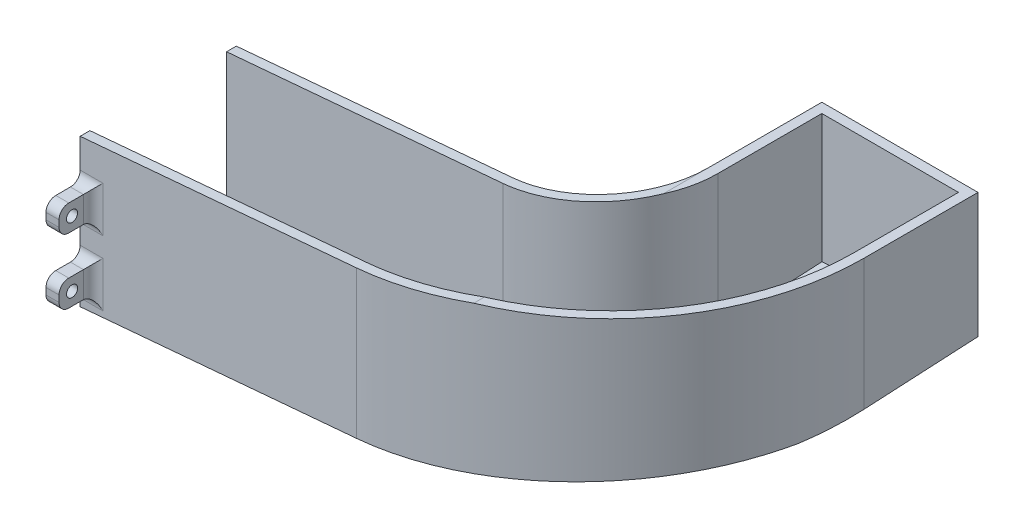
SolidWorks part; units mm, degrees
ref_plane "Front Plane" through (0, 0, 0) normal (0, 0, 1) x (1, 0, 0)
ref_plane "Top Plane" through (0, 0, 0) normal (0, 1, 0) x (1, 0, 0)
ref_plane "Right Plane" through (0, 0, 0) normal (1, 0, 0) x (0, 0, -1)
sketch "Sketch2" plane through (0, 0, 0) normal (0, 1, 0) x (1, 0, 0)
  line L1 (0, 0) -> (85, 0)
  line L2 (0, 0) -> (0, 48)
  line L3 (0, 48) -> (85, 48)
  line L8 (115, 78) -> (115, 113)
  line L9 (115, 113) -> (163, 113)
  line L10 (163, 78) -> (163, 113)
  arc A1 (85, 48) -> (115, 78) centre (85, 78) ccw
  arc A2 (85, 0) -> (163, 78) centre (85, 78) ccw
  point P9 (0, 0)
  point P11 (0, 0)
  dimension "D1" = 48
  dimension "D5" = 35
  dimension "D2" = 85
  dimension "D3" = 48
  dimension "D4" = 115
extrude "Boss-Extrude1" add sketch "Sketch2" along normal blind 60
sketch "Sketch3" plane through (0, 0, 0) normal (0, 0, 1) x (1, 0, 0)
  line L0 (0, 0) -> (200, 17.4977)
  line L2 (0, 60) -> (0, 0) construction
  line L3 (200, 0) -> (200, 17.4977)
  line L5 (0, 0) -> (200, 0)
  line L7 (0, 45.39) -> (0, 60)
  line L8 (0, 60) -> (200, 60)
  line L9 (0, 60) -> (85, 60) construction
  line L11 (163, 60) -> (85, 60) construction
  line L12 (0, 45.39) -> (115, 55.4512)
  line L13 (115, 55.4512) -> (200, 55.4512)
  line L14 (200, 55.4512) -> (200, 60)
  point P4 (140.9944, 57.1439)
  point P14 (154.6463, 60)
  point P17 (180.8999, 60)
  point P18 (132.5245, 57.8644)
  point P21 (113.8292, 56.2288)
  point P23 (0, 0)
  dimension "D1" = 45.39
  dimension "D2" = 200
  dimension "D3" = 5
extrude "Cut-Extrude1" cut sketch "Sketch3" against normal through all
sketch "Sketch18" plane through (163, 0, 0) normal (-1, 0, 0) x (0, 0, 1)
  line L0 (-123, 8.2607) -> (-53, 8.2607)
  line L4 (-123, 8.2607) -> (-123, 17.5692)
  line L5 (-48, 45.39) -> (-48, 0) construction
  line L6 (-78, 14.2607) -> (-113, 14.2607) construction
  line L7 (-53, 8.2607) -> (-53, 13.9006)
  line L8 (-53, 13.9006) -> (-123, 17.5692)
  ellipse E3 centre (-78, 7.4365) end of major axis (0, 7.4365) minor radius 6.8241 (0, 7.4365) -> (-78, 14.2607) ccw construction
  dimension "D1" = 3
  dimension "D2" = 70
  dimension "D3" = 6
  dimension "D4" = 5
extrude "Cut-Extrude9" cut sketch "Sketch18" along direction (-0.9962, -0.0872, 0) on the side against the normal blind 55 and the other way blind 55
shell "Shell4" thickness 3 removed face at (67.7517, 51.3175, -28.7169) removed face at (136.38, 55.4512, -76.1467)
sketch "Sketch15" plane through (3, 0, 0) normal (1, 0, 0) x (0, 0, -1)
  line L4 (45, 45.6525) -> (3, 45.6525)
  line L5 (45, 45.6525) -> (3, 45.6525)
  line L8 (3, 45.6525) -> (3, 3.2739)
  line L9 (3, 3.2739) -> (45, 3.2739)
  line L10 (45, 3.2739) -> (45, 45.6525)
  line L12 (3, 45.6525) -> (3, 3.2739)
  line L13 (3, 3.2739) -> (45, 3.2739)
  line L14 (45, 3.2739) -> (45, 45.6525)
  dimension "D1" = 0
extrude "Cut-Extrude8" cut sketch "Sketch15" against normal up to surface (3 mm away) up to face at (0, 22.695, -24)
sketch "Sketch16" plane through (0, 0, 0) normal (-1, 0, 0) x (0, 0, 1)
  line L1 (-1.5, 33.39) -> (10.5, 33.39)
  line L2 (-1.5, 33.39) -> (-1.5, 25.39)
  line L3 (-1.5, 25.39) -> (10.5, 25.39)
  line L4 (10.5, 33.39) -> (10.5, 25.39)
  line L5 (0, 45.39) -> (0, 0) construction
  line L7 (-3, 45.39) -> (0, 45.39) construction
  line L8 (-1.5, 13.39) -> (10.5, 13.39)
  line L13 (-1.5, 13.39) -> (-1.5, 5.39)
  line L14 (-1.5, 5.39) -> (10.5, 5.39)
  line L15 (10.5, 13.39) -> (10.5, 5.39)
  line L16 (-24, 0) -> (-24, 60) construction
  line L17 (-48, 0) -> (0, 0) construction
  line L18 (-58.5, 13.39) -> (-58.5, 5.39)
  line L19 (-46.5, 5.39) -> (-58.5, 5.39)
  line L20 (-46.5, 13.39) -> (-46.5, 5.39)
  line L21 (-46.5, 13.39) -> (-58.5, 13.39)
  line L22 (-58.5, 33.39) -> (-58.5, 25.39)
  line L23 (-46.5, 25.39) -> (-58.5, 25.39)
  line L24 (-46.5, 33.39) -> (-46.5, 25.39)
  line L25 (-46.5, 33.39) -> (-58.5, 33.39)
  circle A0 centre (6.5, 29.39) radius 1.7
  circle A2 centre (6.5, 9.39) radius 1.7
  circle A3 centre (-54.5, 9.39) radius 1.7
  circle A4 centre (-54.5, 29.39) radius 1.7
  point P10 (10.5, 29.39)
  dimension "D1" = 3.4
  dimension "D2" = 8
  dimension "D3" = 4
  dimension "D4" = 1.5
  dimension "D5" = 12
  dimension "D6" = 8
  dimension "D7" = 2
  dimension "D8" = 20
  dimension "D9" = 60
extrude "Boss-Extrude2" add sketch "Sketch16" against normal blind 4
fillet "Fillet1" radius 3 20 edges at (2, 5.39, 10.5) (2, 5.39, 0) (4, 9.39, 0) (2, 13.39, 10.5) (2, 13.39, 0) (2, 25.39, 10.5) (2, 25.39, 0) (4, 29.39, 0) (2, 33.39, 0) (2, 33.39, 10.5) (2, 13.39, -58.5) (2, 5.39, -58.5) (2, 5.39, -48) (4, 9.39, -48) (2, 13.39, -48) (4, 29.39, -48) (2, 25.39, -48) (2, 25.39, -58.5) (2, 33.39, -48) (2, 33.39, -58.5)
